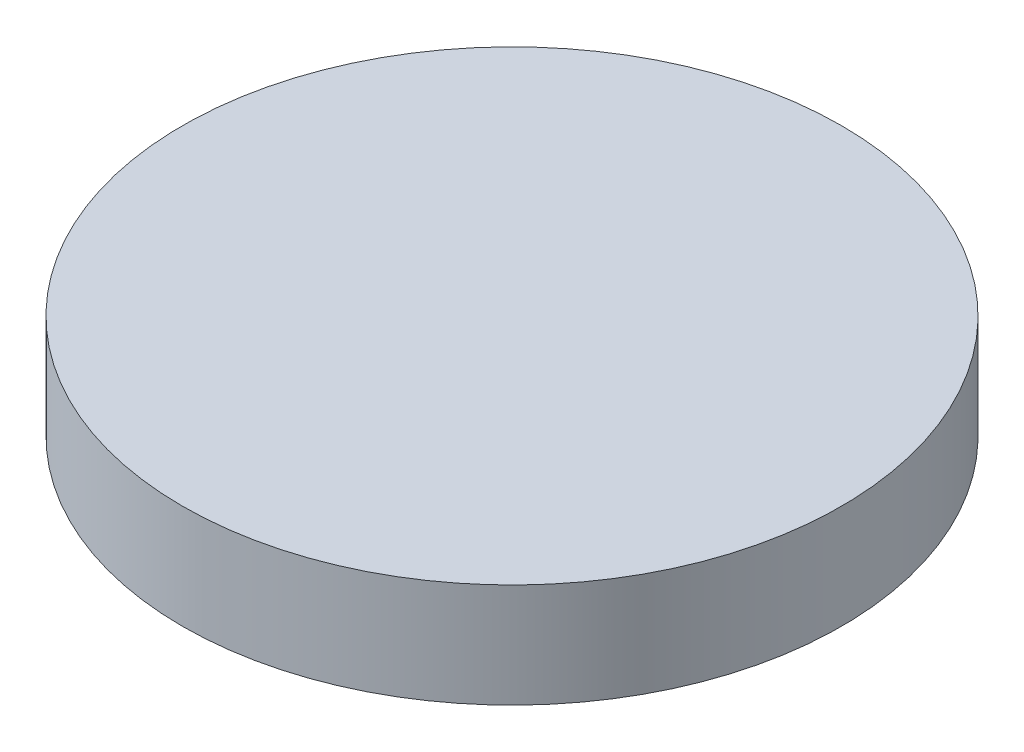
SolidWorks part; units mm, degrees
ref_plane "Front Plane" through (0, 0, 0) normal (0, 0, 1) x (1, 0, 0)
ref_plane "Top Plane" through (0, 0, 0) normal (0, 1, 0) x (1, 0, 0)
ref_plane "Right Plane" through (0, 0, 0) normal (1, 0, 0) x (0, 0, -1)
sketch "Sketch1" plane through (0, 0, 0) normal (0, 1, 0) x (1, 0, 0)
  circle A0 centre (0, 0) radius 60.325
  dimension "D1" = 120.65
extrude "Boss-Extrude1" add sketch "Sketch1" along normal blind 19.05
sketch "Sketch2" plane through (0, 0, 0) normal (0, -1, 0) x (1, 0, 0)
  circle A0 centre (0, 0) radius 57.15
  circle A1 centre (0, 0) radius 55.5625
  dimension "D1" = 114.3
  dimension "D2" = 111.125
extrude "Cut-Extrude1" cut sketch "Sketch2" against normal blind 3.175
